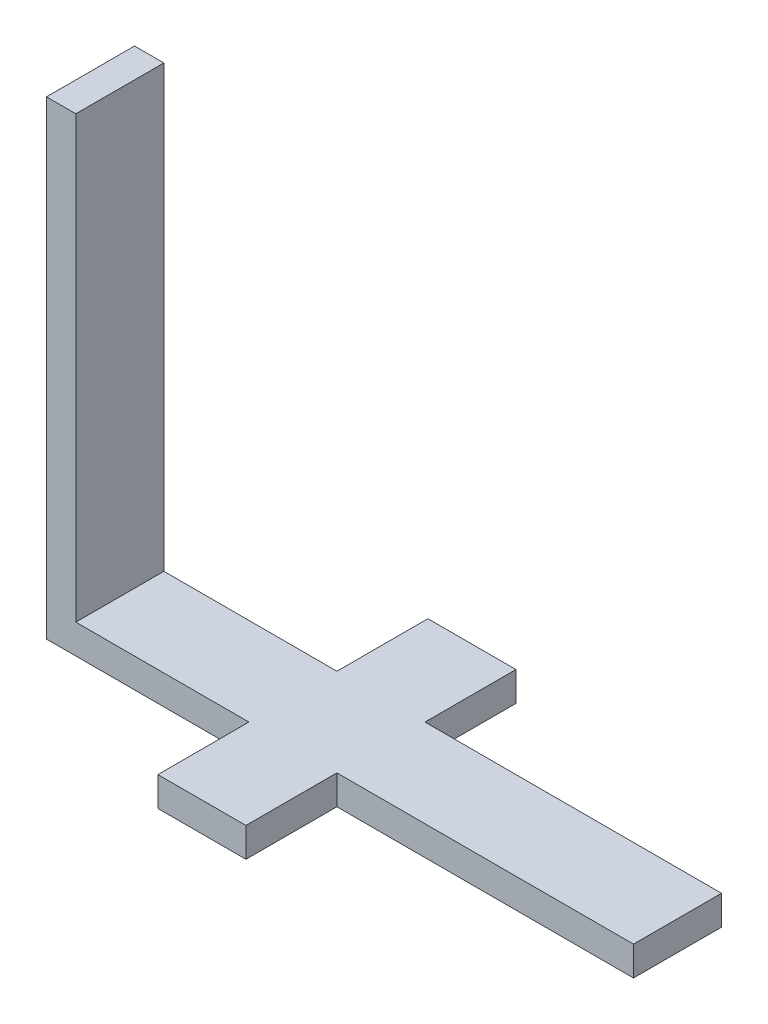
SolidWorks part; units mm, degrees
ref_plane "Front Plane" through (0, 0, 0) normal (0, 0, 1) x (1, 0, 0)
ref_plane "Top Plane" through (0, 0, 0) normal (0, 1, 0) x (1, 0, 0)
ref_plane "Right Plane" through (0, 0, 0) normal (1, 0, 0) x (0, 0, -1)
sketch "Sketch1" plane through (0, 0, 0) normal (0, 1, 0) x (1, 0, 0)
  line L1 (-53.3412, 17.0332) -> (46.6588, 17.0332)
  line L2 (-53.3412, 17.0332) -> (-53.3412, 2.0332)
  line L3 (-53.3412, 2.0332) -> (46.6588, 2.0332)
  line L4 (46.6588, 17.0332) -> (46.6588, 2.0332)
  dimension "D1" = 100
  dimension "D2" = 15
extrude "Boss-Extrude1" add sketch "Sketch1" along normal blind 5
sketch "Sketch2" plane through (0, 5, 0) normal (0, 1, 0) x (1, 0, 0)
  line L0 (-53.3412, 17.0332) -> (-48.3412, 17.0332)
  line L1 (46.6588, 17.0332) -> (-53.3412, 17.0332) construction
  line L2 (-53.3412, 2.0332) -> (-48.3412, 2.0332)
  line L3 (-53.3412, 2.0332) -> (46.6588, 2.0332) construction
  line L4 (-48.3412, 17.0332) -> (-48.3412, 2.0332)
  line L5 (-53.3412, 17.0332) -> (-53.3412, 2.0332)
extrude "Boss-Extrude2" add sketch "Sketch2" along normal blind 75
sketch "Sketch3" plane through (0, 0, 0) normal (0, -1, 0) x (-1, 0, 0)
  line L0 (53.3412, 2.0332) -> (11.3612, 2.0332) construction
  line L1 (53.3412, 2.0332) -> (-46.6588, 2.0332) construction
  line L2 (11.3612, 2.0332) -> (11.3612, -8.4668) construction
  line L3 (11.3612, 17.0332) -> (11.3612, 32.5332) construction
  line L4 (-46.6588, 17.0332) -> (53.3412, 17.0332) construction
  line L5 (11.3612, 32.5332) -> (18.8612, 32.5332)
  line L6 (18.8612, 32.5332) -> (11.3612, 32.5332)
  line L7 (18.8612, -13.4668) -> (3.8612, -13.4668)
  line L8 (11.3612, 32.5332) -> (3.8612, 32.5332)
  line L9 (18.8612, 32.5332) -> (18.8612, 17.0332)
  line L10 (18.8612, 17.0332) -> (3.8612, 17.0332)
  line L11 (3.8612, 17.0332) -> (3.8612, 32.5332)
  line L12 (18.8612, -13.4668) -> (18.8612, 2.0332)
  line L13 (18.8612, 2.0332) -> (3.8612, 2.0332)
  line L14 (3.8612, 2.0332) -> (3.8612, -13.4668)
  line M5 (53.3412, 17.0332) -> (-46.6588, 17.0332)
  line M7 (-46.6588, 2.0332) -> (53.3412, 2.0332)
extrude "Boss-Extrude3" add sketch "Sketch3" against normal blind 5 contours L11 L9 L5 L8 M5 | L14 L7 L12 M7 region at (-11.3612, 0, -24.7832) region at (-11.3612, 0, 5.7168)
sketch "Sketch4" plane through (0, 0, 0) normal (0, -1, 0) x (-1, 0, 0)
  line L0 (-46.6588, 9.5332) -> (53.3412, 9.5332)
  line L1 (-46.6588, 2.0332) -> (-46.6588, 17.0332) construction
  line L2 (53.3412, 17.0332) -> (53.3412, 2.0332) construction
sketch "Sketch5" plane through (-53.3412, 0, 0) normal (-1, 0, 0) x (0, 0, 1)
  line L0 (-9.5332, 0) -> (-9.5332, 15)
  line L1 (-17.0332, 0) -> (-2.0332, 0) construction
  line L2 (-9.5332, 80) -> (-9.5332, 65)
  line L3 (-17.0332, 80) -> (-2.0332, 80) construction
